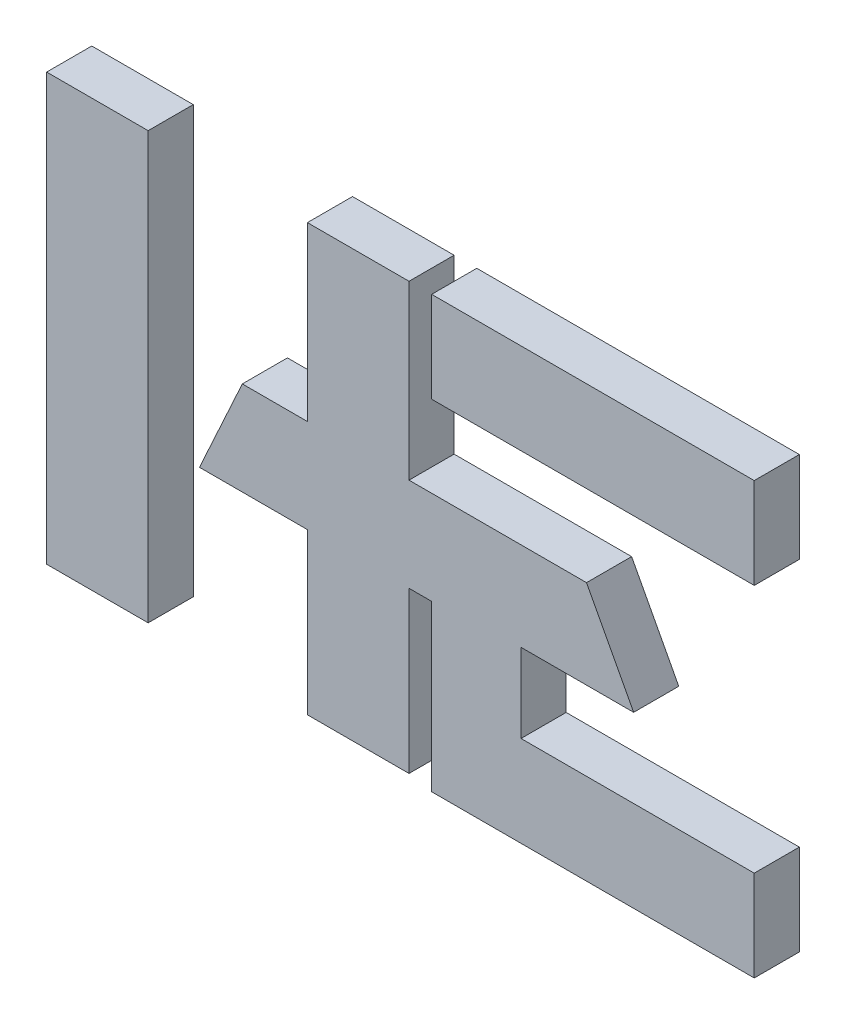
SolidWorks part; units mm, degrees
ref_plane "Front Plane" through (0, 0, 0) normal (0, 0, 1) x (1, 0, 0)
ref_plane "Top Plane" through (0, 0, 0) normal (0, 1, 0) x (1, 0, 0)
ref_plane "Right Plane" through (0, 0, 0) normal (1, 0, 0) x (0, 0, -1)
sketch "Sketch1" plane through (0, 0, 0) normal (0, 0, 1) x (1, 0, 0)
  line L0 (-3.8951, 1.0348) -> (-4.9505, -1.272)
  line L1 (-8.7145, 5.2778) -> (-6.2145, 5.2778)
  line L2 (-8.7145, 5.2778) -> (-8.7145, -5.2222)
  line L3 (-8.7145, -5.2222) -> (-6.2145, -5.2222)
  line L4 (-6.2145, 5.2778) -> (-6.2145, -5.2222)
  line L5 (8.7145, 5.2778) -> (0.7689, 5.2778)
  line L6 (8.7145, 5.2778) -> (8.7145, 3.0408)
  line L7 (8.7145, 3.0408) -> (0.7689, 3.0408)
  line L8 (0.7689, 5.2778) -> (0.7689, 3.0408)
  line L9 (8.7145, -3.0963) -> (2.9702, -3.0963)
  line L10 (8.7145, -3.0963) -> (8.7145, -5.3334)
  line L11 (8.7145, -5.3334) -> (0.7689, -5.3334)
  line L13 (0.7689, -5.3334) -> (0.7689, -1.272)
  line L14 (0.7689, 1.0348) -> (2.9702, 1.0348)
  line L15 (2.9702, -3.0963) -> (2.9702, -1.1514)
  line L16 (2.9702, 1.0348) -> (4.5834, 1.0348)
  line L17 (2.9702, -1.1514) -> (4.5834, -1.1514)
  line L18 (0.7689, -1.272) -> (0.2111, -1.272)
  line L19 (0.7689, 1.0348) -> (0.2111, 1.0348)
  line L20 (0.2111, 5.2778) -> (-2.2917, 5.2778)
  line L21 (0.2111, 5.2778) -> (0.2111, 1.0348)
  line L22 (0.2111, -5.2222) -> (-2.2917, -5.2222)
  line L23 (-2.2917, 5.2778) -> (-2.2917, 1.0348)
  line L24 (-4.9505, -1.272) -> (-3.8553, -1.272)
  line L25 (4.5834, -1.1514) -> (5.7443, -1.1514)
  line L26 (5.7443, -1.1514) -> (4.5834, 1.0348)
  line L27 (-2.2917, 1.0348) -> (-3.8951, 1.0348)
  line L28 (0.2111, -1.272) -> (0.2111, -5.2222)
  line L29 (-2.2917, -1.272) -> (-2.2917, -5.2222)
  line L30 (-2.2917, -1.272) -> (-3.8553, -1.272)
  line L31 (8.7145, 3.0408) -> (8.7145, -3.0963) construction
  line L32 (8.7145, -0.0278) -> (-8.7145, 0.0278) construction
  line L33 (0, 5.2222) -> (0, -5.2222) construction
  point P35 (0, 0)
  dimension "D1" = 2.5
  dimension "D2" = 10.5
  dimension "D3" = 10.5
  dimension "D4" = 4.243
  dimension "D5" = 2.3068
  dimension "D6" = 0.5578
  dimension "D7" = 2.2012
  dimension "D8" = 1.6132
  dimension "D9" = 2.1862
  dimension "D10" = 1.1609
  dimension "D11" = 1.6132
  dimension "D12" = 1.9449
  dimension "D13" = 5.7443
  dimension "D14" = 7.9456
  dimension "D15" = 0.5578
  dimension "D16" = 2.5028
  dimension "D17" = 7.9456
  dimension "D18" = 2.006
  dimension "D19" = 3.9228
  dimension "D20" = 0.5578
  dimension "D21" = 1.0554
  dimension "D22" = 1.0953
  dimension "D23" = 1.264
extrude "Boss-Extrude1" add sketch "Sketch1" along normal blind 2
scale "Scale2" bodies to scale 101 103 102 scale about origin uniform scaling yes scale factor 1.8
sketch "Sketch2" plane through (0, 0, 3.6) normal (0, 0, 1) x (1, 0, 0)
  line L1 (-23.7961, 16.7407) -> (26.8273, 16.7407)
  line L2 (-23.7961, 16.7407) -> (-23.7961, -20.2035)
  line L3 (-23.7961, -20.2035) -> (26.8273, -20.2035)
  line L4 (26.8273, 16.7407) -> (26.8273, -20.2035)
  point P4 (-18.8219, 12.2328)
  point P5 (20.195, -14.2448)
  point P6 (-23.7961, 16.7407)
  point P7 (26.8273, -20.2035)
extrude "Cut-Extrude1" cut sketch "Sketch2" against normal blind 1.6
